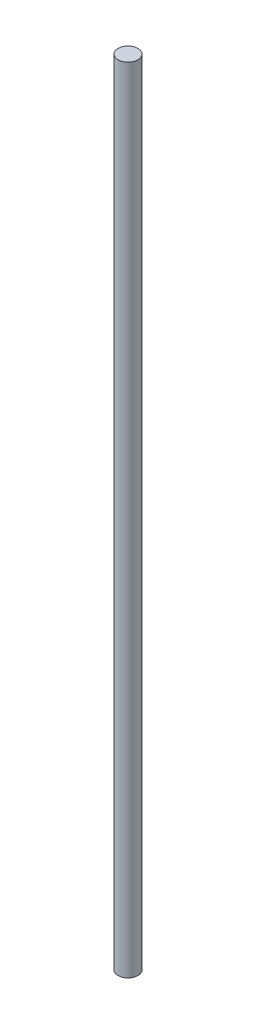
SolidWorks part; units mm, degrees
ref_plane "Front Plane" through (0, 0, 0) normal (0, 0, 1) x (1, 0, 0)
ref_plane "Top Plane" through (0, 0, 0) normal (0, 1, 0) x (1, 0, 0)
ref_plane "Right Plane" through (0, 0, 0) normal (1, 0, 0) x (0, 0, -1)
sketch "Sketch2" plane through (0, 0, 0) normal (0, 1, 0) x (1, 0, 0)
  circle A0 centre (0, 0) radius 5
  dimension "D1" = 10
extrude "Boss-Extrude1" add sketch "Sketch2" along normal blind 400
